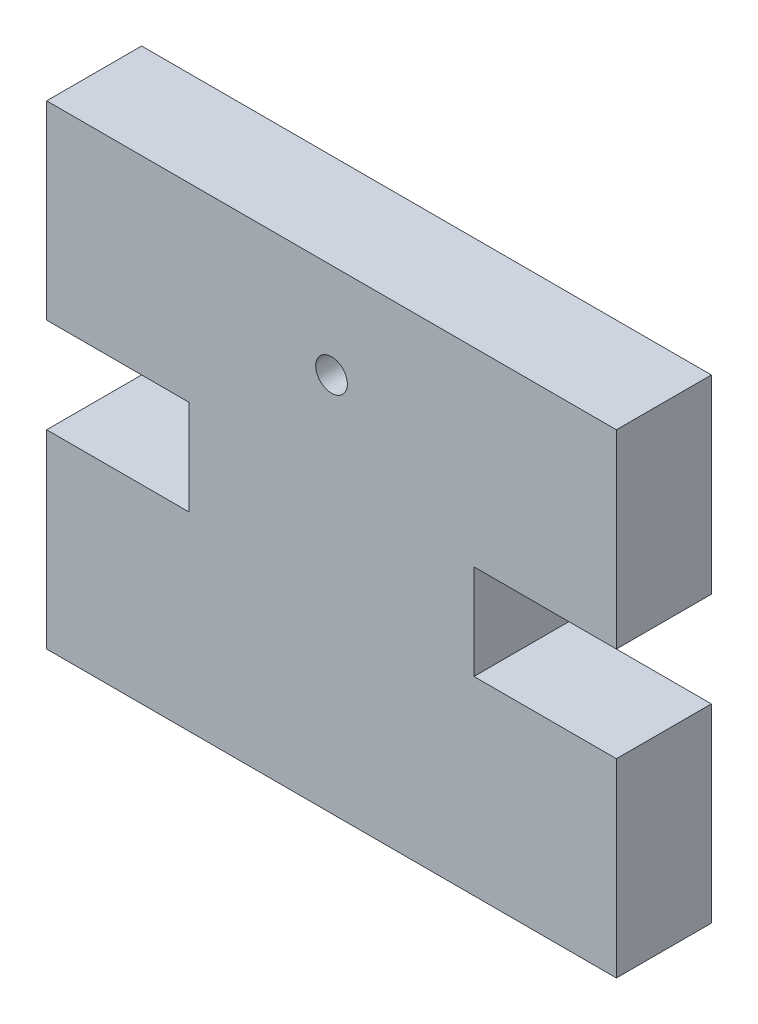
SolidWorks part; units mm, degrees
ref_plane "Front Plane" through (0, 0, 0) normal (0, 0, 1) x (1, 0, 0)
ref_plane "Top Plane" through (0, 0, 0) normal (0, 1, 0) x (1, 0, 0)
ref_plane "Right Plane" through (0, 0, 0) normal (1, 0, 0) x (0, 0, -1)
sketch "Sketch1" plane through (0, 0, 0) normal (0, 0, 1) x (1, 0, 0)
  line L0 (0, 0) -> (-4.5, 0)
  line L1 (-4.5, 0) -> (-4.5, -6)
  line L2 (0, 0) -> (0, 3)
  line L3 (-4.5, -6) -> (13.5, -6)
  line L4 (9, 0) -> (9, 3)
  line L5 (4.5, -6) -> (4.5, 6) construction
  line L6 (13.5, 0) -> (13.5, -6)
  line L7 (9, 0) -> (13.5, 0)
  line L8 (0, 3) -> (-4.5, 3)
  line L9 (-4.5, 3) -> (-4.5, 9)
  line L10 (-4.5, 9) -> (13.5, 9)
  line L11 (13.5, 3) -> (13.5, 9)
  line L12 (9, 3) -> (13.5, 3)
  circle A1 centre (4.5, 6) radius 0.5
  point P17 (4.5, 9)
  dimension "D3" = 1
  dimension "D4" = 18
  dimension "D1" = 9
  dimension "D2" = 18
  dimension "D5" = 6
  dimension "D6" = 3
  dimension "D7" = 6
  dimension "D8" = 3
extrude "Boss-Extrude1" add sketch "Sketch1" along normal blind 3
